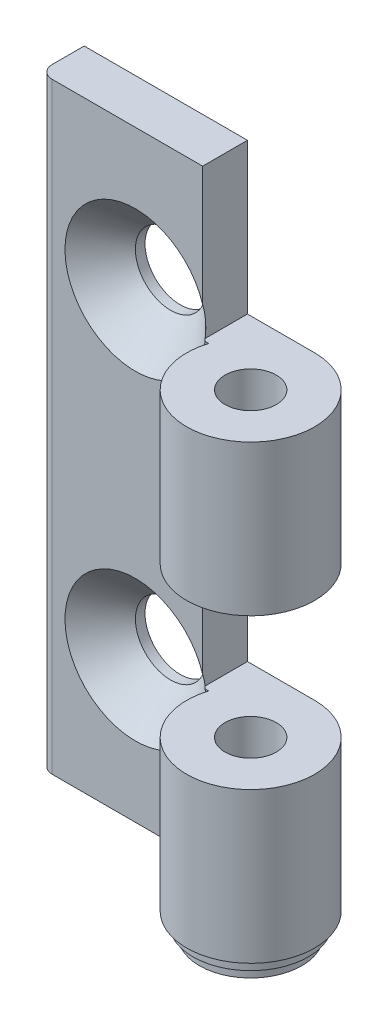
SolidWorks part; units mm, degrees
material "6063-T5"
ref_plane "Front Plane" through (0, 0, 0) normal (0, 0, 1) x (1, 0, 0)
ref_plane "Top Plane" through (0, 0, 0) normal (0, 1, 0) x (1, 0, 0)
ref_plane "Right Plane" through (0, 0, 0) normal (1, 0, 0) x (0, 0, -1)
ref_plane "Plane1" through (0, 0, 0) normal (0, 0, 1) x (1, 0, 0)
sketch "Sketch1" plane through (0, 0, 0) normal (0, 0, 1) x (1, 0, 0)
  line L0 (0, 23.5) -> (5, 23.5)
  line L1 (5, 23.5) -> (5, -23.5)
  line L2 (5, -23.5) -> (0, -23.5)
  line L3 (0, -23.5) -> (0, 23.5)
  line L4 (0, -23.5) -> (0, 23.5) construction
revolve "Revolve1" add sketch "Sketch1" angle 360 about L4 reverse direction yes
ref_plane "Plane2" through (0, 0, -5) normal (0, 0, 1) x (1, 0, 0)
sketch "Sketch2" plane through (0, 0, -5) normal (0, 0, 1) x (1, 0, 0)
  line L0 (-18, 23.5) -> (-18, -23.5)
  line L1 (-18, -23.5) -> (0, -23.5)
  line L2 (0, -23.5) -> (0, 23.5)
  line L3 (0, 23.5) -> (-18, 23.5)
extrude "Boss-Extrude1" add sketch "Sketch2" along normal blind 3.5
ref_plane "Plane3" through (0, 0, 0) normal (0, 0, 1) x (1, 0, 0)
sketch "Sketch3" plane through (0, 0, 0) normal (0, 0, 1) x (1, 0, 0)
  line L0 (-47, 47) -> (-47, -47)
  line L1 (-47, -47) -> (47, -47)
  line L2 (47, -47) -> (47, 47)
  line L3 (47, 47) -> (-47, 47)
  line L4 (-18, -23.5) -> (5, -23.5)
  line L5 (5, -23.5) -> (5, -11.75)
  line L6 (5, -11.75) -> (-5.25, -11.75)
  line L7 (-5.25, -11.75) -> (-5.25, 0)
  line L8 (-5.25, 0) -> (5, 0)
  line L9 (5, 0) -> (5, 11.75)
  line L10 (5, 11.75) -> (-5.25, 11.75)
  line L11 (-5.25, 11.75) -> (-5.25, 23.5)
  line L12 (-5.25, 23.5) -> (-18, 23.5)
  line L13 (-18, 23.5) -> (-18, -23.5)
extrude "Cut-Extrude1" cut sketch "Sketch3" against normal blind 47 and the other way blind 47
ref_plane "Plane4" through (0, 0, 0) normal (0, 0, 1) x (1, 0, 0)
sketch "Sketch4" plane through (0, 0, 0) normal (0, 0, 1) x (1, 0, 0)
  line L0 (0, -23.5) -> (4.5, -23.5)
  line L1 (4.5, -23.5) -> (4.5, -24.35)
  line L2 (4.5, -24.35) -> (4, -24.35)
  line L3 (4, -24.35) -> (4, -25.2)
  line L4 (4, -25.2) -> (0, -25.2)
  line L5 (0, -25.2) -> (0, -23.5)
  line L6 (0, -25.2) -> (0, -23.5) construction
revolve "Revolve2" add sketch "Sketch4" angle 360 about L6 reverse direction yes
ref_plane "Plane5" through (0, 0, 0) normal (0, 0, 1) x (1, 0, 0)
sketch "Sketch5" plane through (0, 0, 0) normal (0, 0, 1) x (1, 0, 0)
  line L0 (0, 26.7) -> (2, 26.7)
  line L1 (2, 26.7) -> (2, -26.7)
  line L2 (2, -26.7) -> (0, -26.7)
  line L3 (0, -26.7) -> (0, 26.7)
  line L4 (0, -26.7) -> (0, 26.7) construction
revolve "Cut-Revolve1" cut sketch "Sketch5" angle 360 about L4 reverse direction yes
ref_plane "Plane6" through (-10.5, 0, 0) normal (1, 0, 0) x (0, 0, -1)
sketch "Sketch6" plane through (-10.5, 0, 0) normal (1, 0, 0) x (0, 0, -1)
  line L0 (5, -12.5) -> (5, -15.25)
  line L1 (5, -15.25) -> (4.25, -15.25)
  line L2 (4.25, -15.25) -> (1.5, -18)
  line L3 (1.5, -18) -> (1.5, -12.5)
  line L4 (1.5, -12.5) -> (5, -12.5)
  line L5 (1.5, -12.5) -> (5, -12.5) construction
revolve "Cut-Revolve2" cut sketch "Sketch6" angle 360 about L5 reverse direction yes
ref_plane "Plane7" through (-10.5, 0, 0) normal (1, 0, 0) x (0, 0, -1)
sketch "Sketch7" plane through (-10.5, 0, 0) normal (1, 0, 0) x (0, 0, -1)
  line L0 (5, 12.5) -> (5, 9.75)
  line L1 (5, 9.75) -> (4.25, 9.75)
  line L2 (4.25, 9.75) -> (1.5, 7)
  line L3 (1.5, 7) -> (1.5, 12.5)
  line L4 (1.5, 12.5) -> (5, 12.5)
  line L5 (1.5, 12.5) -> (5, 12.5) construction
revolve "Cut-Revolve3" cut sketch "Sketch7" angle 360 about L5 reverse direction yes
ref_plane "Plane8" through (0, 0, 0) normal (0, 1, 0) x (1, 0, 0)
sketch "Sketch8" plane through (0, 0, 0) normal (0, 1, 0) x (1, 0, 0)
  line L0 (-18, 2.5) -> (-18, 1.5)
  line L1 (-18, 1.5) -> (-17, 1.5)
  arc A0 (-17, 1.5) -> (-18, 2.5) centre (-17, 2.5) cw
extrude "Cut-Extrude2" cut sketch "Sketch8" against normal blind 23.5 and the other way blind 23.5
